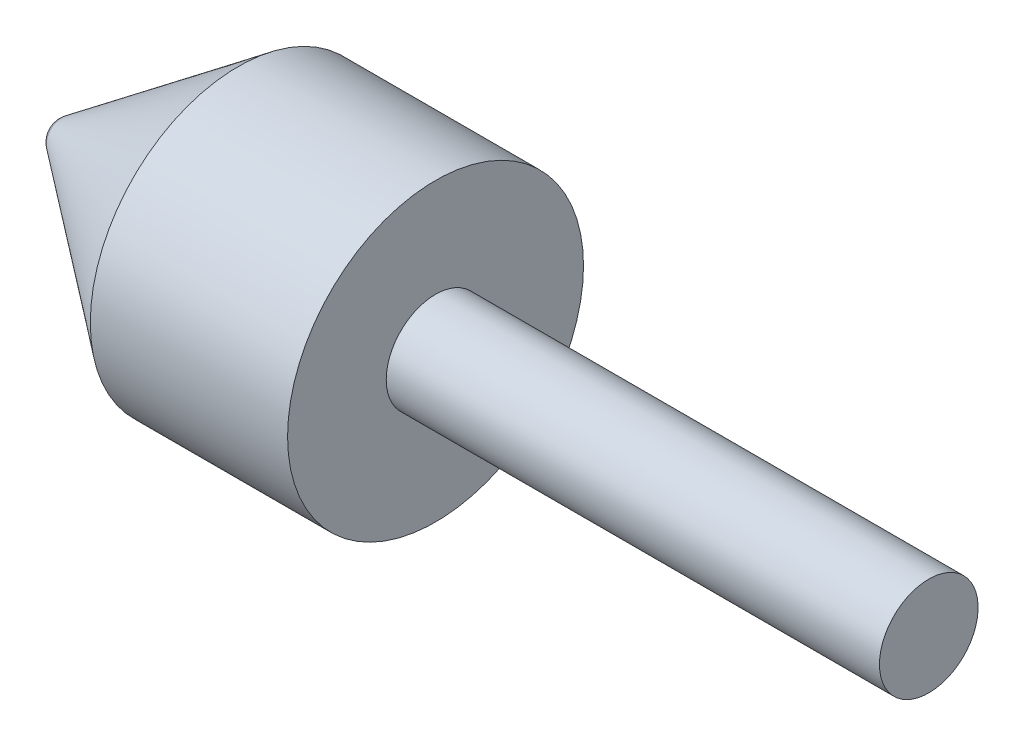
SolidWorks part; units mm, degrees
ref_plane "Plan de face" through (0, 0, 0) normal (0, 0, 1) x (1, 0, 0)
ref_plane "Plan de dessus" through (0, 0, 0) normal (0, 1, 0) x (1, 0, 0)
ref_plane "Plan de droite" through (0, 0, 0) normal (1, 0, 0) x (0, 0, -1)
sketch "Sketch1" plane through (0, 0, 0) normal (0, 0, 1) x (1, 0, 0)
  line L0 (0, 0) -> (0, 0.5)
  line L1 (0, 0.5) -> (-5, 0.5)
  line L2 (-5, 0.5) -> (-5, 1.5)
  line L3 (-5, 1.5) -> (-7, 1.5)
  line L4 (-8.8667, 0) -> (0, 0)
  line L5 (-8.7867, 0.16) -> (-7, 1.5)
  arc A0 (-8.8667, 0) -> (-8.7867, 0.16) centre (-8.6667, 0) cw
  dimension "D6" = 0.2
  dimension "D1" = 0.5
  dimension "D2" = 5
  dimension "D3" = 1
  dimension "D4" = 2
  dimension "D5" = 8.8667
  dimension "D7" = 2.2333
revolve "Revolve1" add sketch "Sketch1" angle 360 about L4
